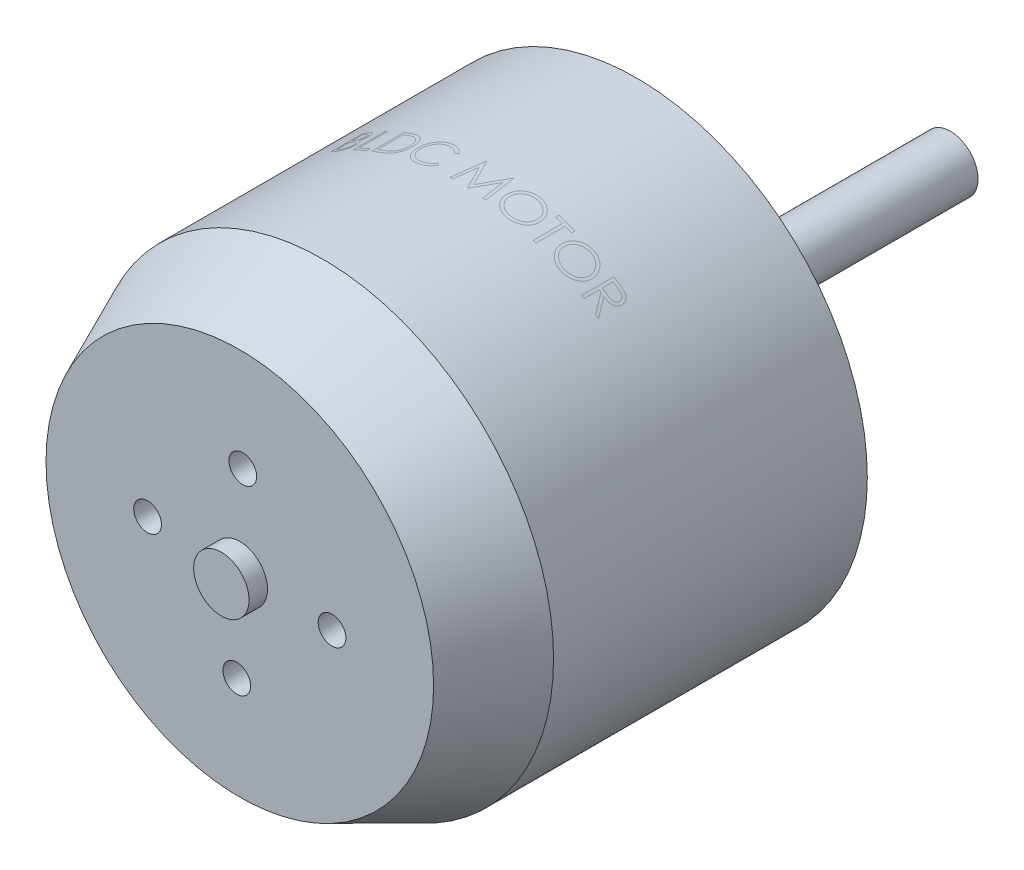
SolidWorks part; units mm, degrees
ref_plane "Front Plane" through (0, 0, 0) normal (0, 0, 1) x (1, 0, 0)
ref_plane "Top Plane" through (0, 0, 0) normal (0, 1, 0) x (1, 0, 0)
ref_plane "Right Plane" through (0, 0, 0) normal (1, 0, 0) x (0, 0, -1)
sketch "Sketch1" plane through (0, 0, 0) normal (0, 1, 0) x (1, 0, 0)
  line L0 (10.7322, 17.9332) -> (-14.2678, 17.9332)
  line L1 (-14.2678, 17.9332) -> (-14.2678, -25.0668)
  line L2 (-14.2678, -25.0668) -> (10.7322, -25.0668)
  line L3 (10.7322, -25.0668) -> (10.7322, 17.9332)
  line L4 (-14.2678, 17.9332) -> (-14.2678, -25.0668) construction
revolve "Revolve1" add sketch "Sketch1" angle 360 about L4 reverse direction yes
sketch "Sketch2" plane through (0, 0, 25.0668) normal (0, 0, 1) x (1, 0, 0)
  circle A0 centre (-14.2678, 0) radius 3
extrude "Boss-Extrude1" add sketch "Sketch2" along normal blind 2
sketch "Sketch3" plane through (0, 0, -17.9332) normal (0, 0, -1) x (-1, 0, 0)
  circle A0 centre (14.2678, 0) radius 3
extrude "Boss-Extrude2" add sketch "Sketch3" along normal blind 34
hole_wizard "Ø3.0 (3) Diameter Hole1" positions "Sketch5" profile "Sketch4" hole size "Ø3.0" standard "ANSI Metric"
sketch "Sketch5" plane through (0, 0, 25.0668) normal (0, 0, 1) x (1, 0, 0)
  point P0 (-24.2624, 0.3267)
  point P1 (-14.5945, -9.9947)
  point P2 (-13.9411, 9.9947)
  point P3 (-4.2731, -0.3267)
sketch "Sketch4" plane through (-24.2624, 0.3267, 25.0668) normal (1, 0, 0) x (0, -1, 0)
  line L0 (0, 0) -> (0, 6)
  line L1 (0, 6) -> (1.5, 6)
  line L2 (1.5, 6) -> (1.5, 0)
  line L5 (1.5, 0) -> (0, 0)
  line L10 (0, 6) -> (-1.5, 6) construction
  line L11 (0, -6.35) -> (0, 107.95) construction
  dimension "Hole Dia." = 3
  dimension "Hole Depth" = 6
  dimension "Drill Angle" = 180
chamfer "Chamfer1" distance 4 angle 66.038 1 edges at (10.7322, 0, 25.0668) first distance on face at (-22.7624, 0.3267, 25.0668)
sketch "Sketch6" plane through (0, 0, 0) normal (0, 1, 0) x (1, 0, 0)
  text T0 "BLDC MOTOR"
wrap "Wrap1" sketch "Sketch6" wrap type scribe source sketch "Sketch6" face at (10.7322, 0, 16.0668)
